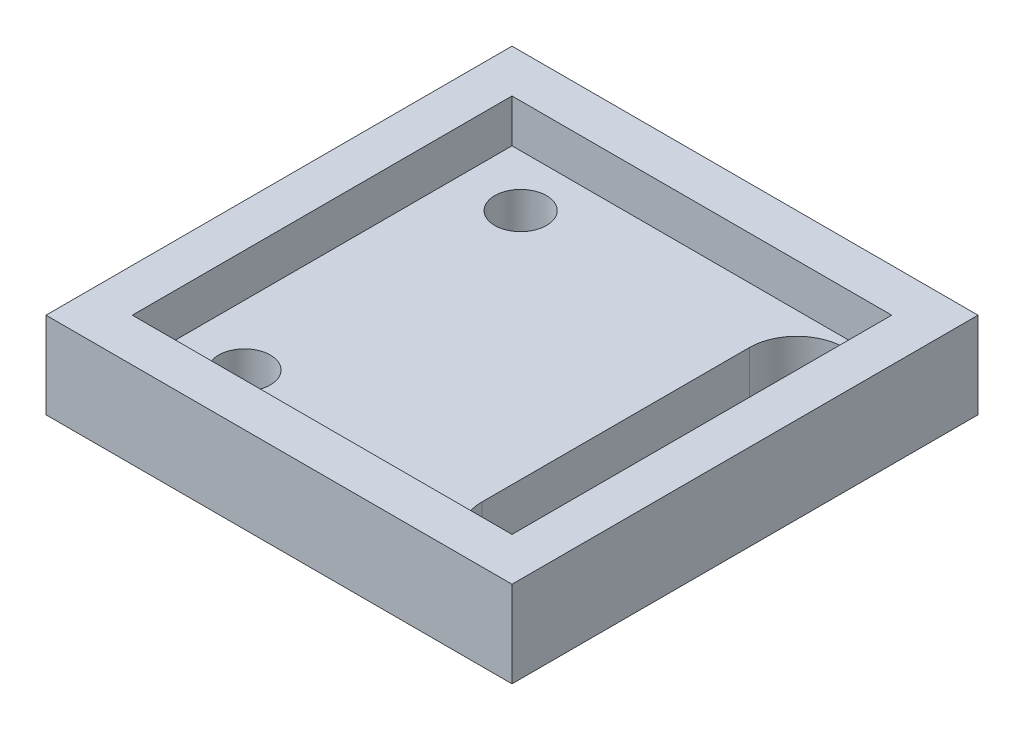
SolidWorks part; units mm, degrees
ref_plane "Front Plane" through (0, 0, 0) normal (0, 0, 1) x (1, 0, 0)
ref_plane "Top Plane" through (0, 0, 0) normal (0, 1, 0) x (1, 0, 0)
ref_plane "Right Plane" through (0, 0, 0) normal (1, 0, 0) x (0, 0, -1)
sketch "Sketch2" plane through (0, 0, 0) normal (0, 1, 0) x (1, 0, 0)
  line L1 (0, 0) -> (27, 0)
  line L2 (0, 0) -> (0, 27)
  line L3 (0, 27) -> (27, 27)
  line L4 (27, 0) -> (27, 27)
  dimension "D1" = 27
  dimension "D2" = 27
extrude "Boss-Extrude1" add sketch "Sketch2" along normal blind 5 contours L2 L1 L4 L3
sketch "Sketch5" plane through (0, 5, 0) normal (0, 1, 0) x (1, 0, 0)
  line L0 (0, 0) -> (27, 0) construction
  line L1 (27, 0) -> (27, 27) construction
  line L5 (2.5, 24.5) -> (24.5, 24.5)
  line L6 (2.5, 24.5) -> (2.5, 2.5)
  line L7 (2.5, 2.5) -> (24.5, 2.5)
  line L8 (24.5, 24.5) -> (24.5, 2.5)
  line L9 (2.5, 24.5) -> (24.5, 2.5) construction
  line L10 (2.5, 2.5) -> (24.5, 24.5) construction
  point P0 (13.5, 13.5)
  dimension "D1" = 22
  dimension "D2" = 22
  dimension "D3" = 2.5
  dimension "D4" = 2.5
extrude "Cut-Extrude2" cut sketch "Sketch5" against normal blind 2.5
sketch "Sketch3" plane through (0, 0, 0) normal (0, -1, 0) x (-1, 0, 0)
  line L3 (0, 27) -> (-27, 27) construction
  circle A1 centre (-6, 21.5) radius 1.5
  circle A2 centre (-6, 5.5) radius 1.5
  dimension "D1" = 3
  dimension "D2" = 3
  dimension "D5" = 16
  dimension "D7" = 6
  dimension "D8" = 5.5
extrude "Cut-Extrude3" cut sketch "Sketch3" against normal blind 10
sketch "Sketch6" plane through (0, 2.5, 0) normal (0, 1, 0) x (1, 0, 0)
  line L0 (0, 27) -> (27, 27) construction
  line L2 (19.5, 21.25) -> (19.5, 5.75)
  line L4 (24.5, 2.5) -> (24.5, 24.5)
  line L5 (24.5, 24.5) -> (2.5, 24.5)
  line L6 (2.5, 24.5) -> (2.5, 2.5)
  line L7 (2.5, 2.5) -> (24.5, 2.5)
  line L8 (24.5, 5.75) -> (24.5, 21.25)
  line L12 (24.5, 21.25) -> (24.5, 5.75)
  line L13 (0, 0) -> (27, 0) construction
  arc A0 (22.25, 3) -> (24.5, 5.75) centre (21.6944, 5.75) ccw
  arc A1 (24.5, 21.25) -> (22.25, 24) centre (21.6944, 21.25) ccw
  arc A2 (19.5, 5.75) -> (22.25, 3) centre (22.25, 5.75) ccw
  arc A3 (22.25, 24) -> (19.5, 21.25) centre (22.25, 21.25) ccw
  line M7 (24.5, 2.5) -> (24.5, 24.5)
  dimension "D2" = 0
  dimension "D3" = 3
  dimension "D4" = 3
  dimension "D1" = 0
extrude "Cut-Extrude4" cut sketch "Sketch6" against normal blind 10 contours A1 A3 L2 A2 A0 M7 region at (22.0014, 2.5, -13.5)
